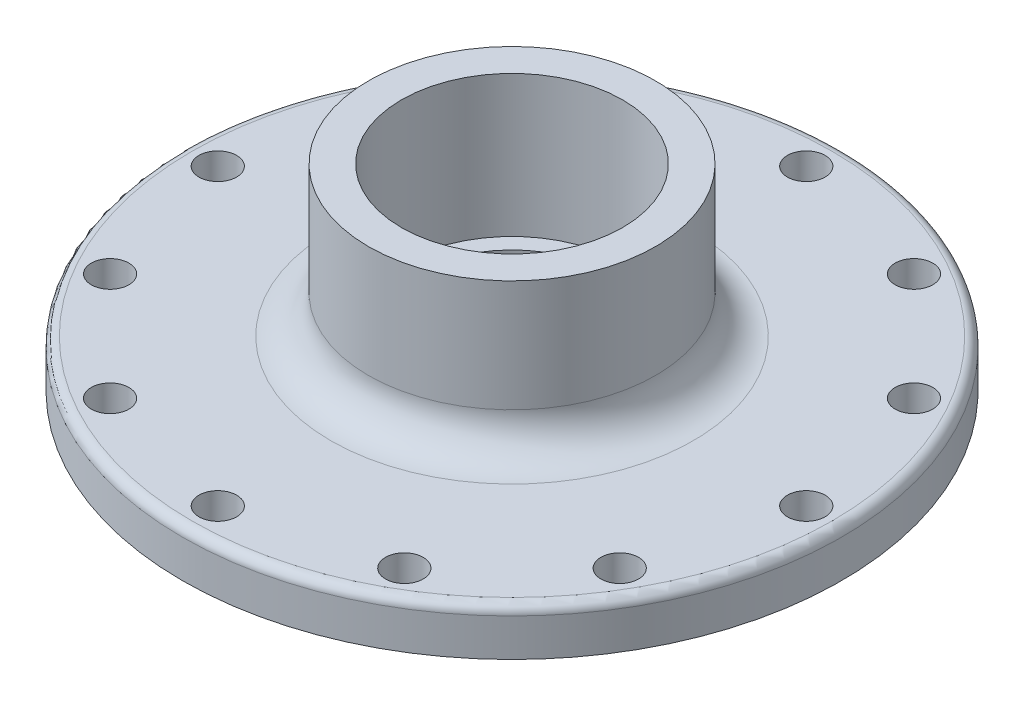
SolidWorks part; units mm, degrees
ref_plane "Front Plane" through (0, 0, 0) normal (0, 0, 1) x (1, 0, 0)
ref_plane "Top Plane" through (0, 0, 0) normal (0, 1, 0) x (1, 0, 0)
ref_plane "Right Plane" through (0, 0, 0) normal (1, 0, 0) x (0, 0, -1)
sketch "Sketch1" plane through (0, 0, 0) normal (0, 0, 1) x (1, 0, 0)
  line L1 (-70, -26.6983) -> (-45, -26.6983)
  line L4 (-23.5, -14.9818) -> (-20, -14.9818)
  line L5 (-20, -14.9818) -> (-20, -26.6983)
  line L18 (-45, -26.6983) -> (-45, -31.6983)
  line L19 (-45, -31.6983) -> (-40, -31.6983)
  line L23 (0, 95.7864) -> (0, -110.3116) construction
  line L27 (-40, -31.6983) -> (-40, -26.6983)
  line L28 (-70, -26.6983) -> (-70, -18.6983)
  line L29 (-68, -16.6983) -> (-38.5, -16.6983)
  line L30 (-30.5, -8.6983) -> (-30.5, 15.0182)
  line L31 (-30.5, 15.0182) -> (-23.5, 15.0182)
  line L32 (-23.5, 15.0182) -> (-23.5, -14.9818)
  line L39 (-20, -26.6983) -> (-40, -26.6983)
  arc A1 (-30.5, -8.6983) -> (-38.5, -16.6983) centre (-38.5, -8.6983) cw
  arc A2 (-70, -18.6983) -> (-68, -16.6983) centre (-68, -18.6983) cw
  point P2 (-21.75, -14.9818)
  point P31 (-70, -16.6983)
  dimension "D1" = 45
  dimension "D2" = 8
  dimension "D7" = 7
  dimension "D13" = 2
  dimension "D3" = 30
  dimension "D4" = 10
  dimension "D5" = 5
  dimension "D6" = 40
  dimension "D8" = 20
revolve "Revolve1" add sketch "Sketch1" angle 360 about L23
sketch "Sketch2" plane through (0, -16.6983, 0) normal (0, 1, 0) x (1, 0, 0)
  circle A0 centre (0, 0) radius 62.5 construction
  point P3 (31.25, -54.1266)
  point P7 (0, -62.5)
  point P8 (-31.25, -54.1266)
  point P9 (-54.1266, -31.25)
  point P10 (-62.5, 0)
  point P11 (-54.1266, 31.25)
  point P12 (-31.25, 54.1266)
  point P13 (0, 62.5)
  point P14 (31.25, 54.1266)
  point P15 (54.1266, 31.25)
  point P16 (62.5, 0)
  point P17 (54.1266, -31.25)
  point P18 (0, 0)
  dimension "D1" = 125
  dimension "D2" = 12
sketch "Sketch4" plane through (0, -16.6983, 0) normal (0, 1, 0) x (1, 0, 0)
  circle A0 centre (0, 0) radius 62.5 construction
  point P3 (0, 62.5)
  point P7 (31.25, 54.1266)
  point P8 (54.1266, 31.25)
  point P9 (62.5, 0)
  point P10 (54.1266, -31.25)
  point P11 (31.25, -54.1266)
  point P12 (0, -62.5)
  point P13 (-31.25, -54.1266)
  point P14 (-54.1266, -31.25)
  point P15 (-62.5, 0)
  point P16 (-54.1266, 31.25)
  point P17 (-31.25, 54.1266)
  dimension "D1" = 125
hole_wizard "Ø8.0mm Dowel Hole2" positions "Sketch4" profile "Sketch5" hole size "Ø8.0" standard "ANSI Metric" end condition through all
sketch "Sketch5" plane through (-31.25, -16.6983, -54.1266) normal (1, 0, 0) x (0, 0, 1)
  line L0 (0, 0) -> (0, 15)
  line L1 (0, 15) -> (4, 15)
  line L2 (4, 15) -> (4, 0)
  line L5 (4, 0) -> (0, 0)
  line L11 (0, -6.35) -> (0, 107.95) construction
  dimension "Thru Hole Dia." = 8
  dimension "Thru Hole Depth" = 15
hole_wizard "Ø8.0mm Dowel Hole1" positions "Sketch2" profile "Sketch3" hole size "Ø8.0" standard "ANSI Metric" end condition through all
sketch "Sketch3" plane through (0, -16.6983, 0) normal (1, 0, 0) x (0, 0, 1)
  line L0 (0, 0) -> (0, 15)
  line L1 (0, 15) -> (4, 15)
  line L2 (4, 15) -> (4, 0)
  line L5 (4, 0) -> (0, 0)
  line L11 (0, -6.35) -> (0, 107.95) construction
  dimension "Thru Hole Dia." = 8
  dimension "Thru Hole Depth" = 15
